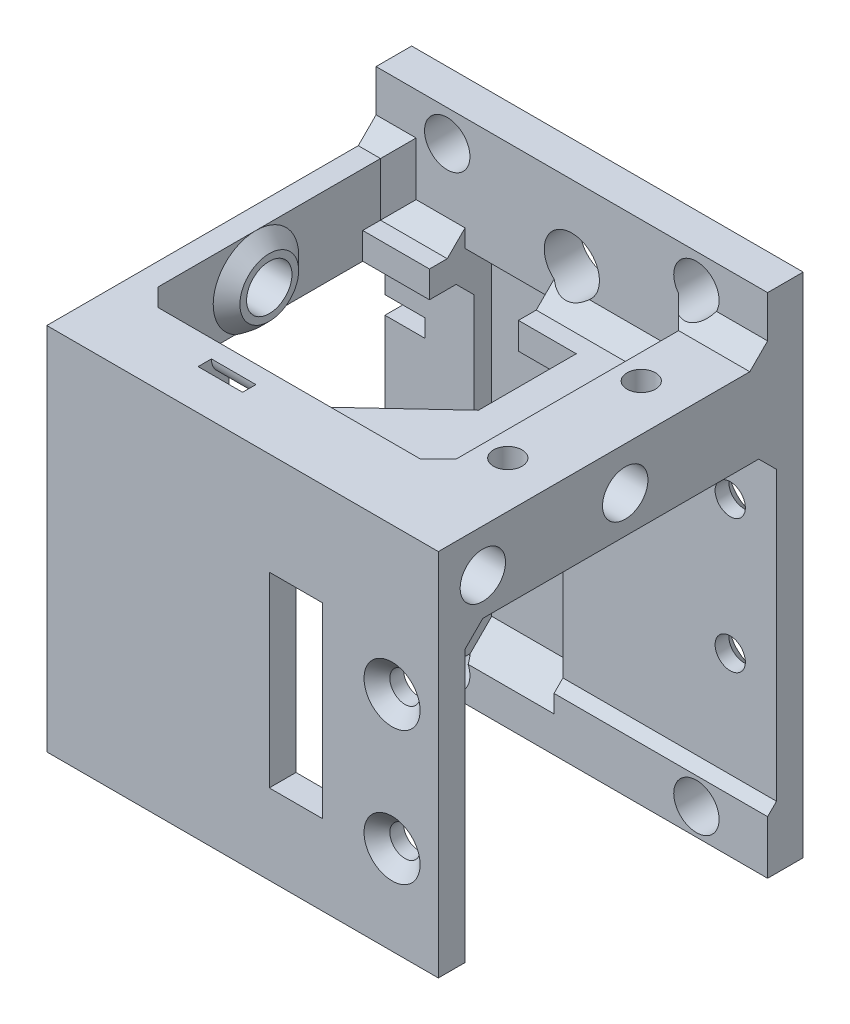
SolidWorks part; units mm, degrees
ref_plane "Front Plane" through (0, 0, 0) normal (0, 0, 1) x (1, 0, 0)
ref_plane "Top Plane" through (0, 0, 0) normal (0, 1, 0) x (1, 0, 0)
ref_plane "Right Plane" through (0, 0, 0) normal (1, 0, 0) x (0, 0, -1)
sketch "Sketch1" plane through (0, 0, 0) normal (0, 1, 0) x (1, 0, 0)
  line L0 (-19.5, 12.5) -> (-19.5, -12.5)
  line L1 (-22, -20.5) -> (22, -20.5)
  line L2 (-22, -20.5) -> (-22, 20.5)
  line L3 (-22, 20.5) -> (22, 20.5)
  line L4 (22, -20.5) -> (22, 20.5)
  line L5 (-22, -20.5) -> (22, 20.5) construction
  line L6 (-22, 20.5) -> (22, -20.5) construction
  line L7 (-19.5, 12.5) -> (4.5, 12.5)
  line L8 (4.5, 12.5) -> (4.5, 1.5)
  line L9 (-19.5, -12.5) -> (-10.5244, -12.5)
  line L10 (-10.5244, -12.5) -> (4.5, 1.5)
  circle A0 centre (16.8, -7.5) radius 1.6
  circle A1 centre (16.8, 7.5) radius 1.6
  point P0 (0, 0)
  dimension "D9" = 3.2
  dimension "D12" = 3.2
  dimension "D1" = 44
  dimension "D2" = 41
  dimension "D3" = 2.5
  dimension "D4" = 25
  dimension "D5" = 8
  dimension "D6" = 24
  dimension "D7" = 11
  dimension "D8" = 5.2
  dimension "D10" = 13
  dimension "D11" = 15
extrude "Boss-Extrude1" add sketch "Sketch1" along normal blind 3
sketch "Sketch2" plane through (0, 3, 0) normal (0, 1, 0) x (1, 0, 0)
  line L0 (-22, 20.5) -> (-22, -20.5) construction
  line L1 (22, 20.5) -> (-22, 20.5)
  line L2 (22, 20.5) -> (22, 16.5)
  line L3 (22, 16.5) -> (-22, 16.5)
  line L4 (-22, 20.5) -> (-22, 16.5)
  dimension "D1" = 4
extrude "Boss-Extrude2" add sketch "Sketch2" along normal blind 12.7
sketch "Sketch3" plane through (0, 0, 0) normal (0, -1, 0) x (1, 0, 0)
  line L0 (22, 20.5) -> (22, -20.5) construction
  line L1 (-22, -20.5) -> (22, -20.5)
  line L2 (-22, -20.5) -> (-22, -17.5)
  line L3 (-22, -17.5) -> (22, -17.5)
  line L4 (22, -20.5) -> (22, -17.5)
  dimension "D1" = 3
extrude "Boss-Extrude3" add sketch "Sketch3" along normal blind 41.3
sketch "Sketch4" plane through (0, 0, 0) normal (0, -1, 0) x (1, 0, 0)
  line L0 (-22, -17.5) -> (-22, 20.5) construction
  line L1 (22, 20.5) -> (-22, 20.5)
  line L2 (22, 20.5) -> (22, 17.5)
  line L3 (22, 17.5) -> (-22, 17.5)
  line L4 (-22, 20.5) -> (-22, 17.5)
  dimension "D1" = 3
extrude "Boss-Extrude4" add sketch "Sketch4" along normal blind 32.5
sketch "Sketch8" plane through (-22, 0, 0) normal (-1, 0, 0) x (0, 0, 1)
  line L0 (-16.5, -35.3) -> (-17.5, -34.3)
  line L1 (-17.5, -41.3) -> (-16.5, -41.3)
  line L2 (-17.5, -41.3) -> (-17.5, -35.3)
  line L3 (-17.5, -35.3) -> (-16.5, -35.3)
  line L4 (-16.5, -41.3) -> (-16.5, -35.3)
  line L5 (-17.5, -41.3) -> (-17.5, 0) construction
  line L6 (-17.5, -34.3) -> (-17.5, -35.3)
  line M5 (-17.5, -41.3) -> (-17.5, 0)
  dimension "D1" = 1
  dimension "D2" = 6
extrude "Boss-Extrude6" add sketch "Sketch8" against normal up to surface (44 mm away) contours L1 L4 L3 M5 | L3 L0 M5 region at (-22, -34.9667, -17.1667) region at (-22, -38.3, -17) up to face at (22, -11.02, -3.3)
sketch "Sketch9" plane through (0, 0, 20.5) normal (0, 0, 1) x (1, 0, 0)
  line L0 (-22, 3) -> (-22, -32.5) construction
  line L1 (3, -23.5) -> (9, -23.5)
  line L2 (3, -23.5) -> (3, -2.5)
  line L3 (3, -2.5) -> (9, -2.5)
  line L4 (9, -23.5) -> (9, -2.5)
  line L5 (22, -32.5) -> (-22, -32.5) construction
  line L6 (22, 3) -> (22, -32.5) construction
  circle A0 centre (16.8, -7.5) radius 1.6
  circle A1 centre (16.8, -22.5) radius 1.6
  dimension "D5" = 3.2
  dimension "D6" = 3.2
  dimension "D1" = 25
  dimension "D2" = 6
  dimension "D3" = 21
  dimension "D4" = 9
  dimension "D7" = 5.2
  dimension "D8" = 5.2
  dimension "D9" = 15
  dimension "D10" = 10
extrude "Cut-Extrude2" cut sketch "Sketch9" against normal up to next
sketch "Sketch12" plane through (0, 3, 0) normal (0, 1, 0) x (1, 0, 0)
  line L0 (-22, 16.5) -> (-22, -20.5) construction
  line L1 (22, -20.5) -> (-22, -20.5)
  line L2 (22, -20.5) -> (22, -12.5)
  line L3 (22, -12.5) -> (-22, -12.5)
  line L4 (-22, -20.5) -> (-22, -12.5)
  line L5 (-19.5, -12.5) -> (-10.5244, -12.5) construction
  line L6 (-19.5, 12.5) -> (-19.5, -12.5) construction
  line L7 (-22, 16.5) -> (-19.5, 16.5)
  line L8 (-22, 16.5) -> (-22, -12.5)
  line L9 (-22, -12.5) -> (-19.5, -12.5)
  line L10 (-19.5, 16.5) -> (-19.5, -12.5)
  line L11 (-22, 16.5) -> (22, 16.5) construction
  line L12 (22, -12.5) -> (14, -12.5)
  line L13 (22, -12.5) -> (22, 16.5)
  line L14 (22, 16.5) -> (14, 16.5)
  line L15 (14, -12.5) -> (14, 16.5)
  circle M6 centre (16.8, 7.5) radius 1.6
  circle M7 centre (16.8, -7.5) radius 1.6
  line M11 (-10.5244, -12.5) -> (-19.5, -12.5)
  line M12 (-19.5, -12.5) -> (-19.5, 12.5)
  line M13 (22, 16.5) -> (-22, 16.5)
  line M14 (-22, 16.5) -> (-22, -20.5)
  line M15 (-22, -20.5) -> (22, -20.5)
  line M16 (22, -20.5) -> (22, 16.5)
  dimension "D1" = 8
extrude "Boss-Extrude7" add sketch "Sketch12" along normal blind 6 contours L15 L3 M16 M13 M7 M6 | L3 M16 M11 M14 M15 | L10 L3 M13 M14 M12 region at (0, 3, 16.5) region at (18.0894, 3, -2.149) region at (-20.75, 3, -2)
sketch "Sketch13" plane through (-22, 0, 0) normal (-1, 0, 0) x (0, 0, 1)
  line L0 (20.5, 9) -> (20.5, -32.5) construction
  line L1 (-17.5, 0) -> (17.5, 0) construction
  line L2 (-17.5, -34.3) -> (-17.5, 0) construction
  circle A0 centre (15.5, 4.2) radius 2.55
  circle A1 centre (-0.5, 4.2) radius 2.55
  dimension "D3" = 5.1
  dimension "D5" = 5.1
  dimension "D1" = 5
  dimension "D2" = 4.2
  dimension "D4" = 17
extrude "Cut-Extrude3" cut sketch "Sketch13" against normal blind 6
sketch "Sketch14" plane through (-19.5, 0, 0) normal (1, 0, 0) x (0, 0, -1)
  circle A0 centre (0.5, 4.2) radius 3.3
  circle A1 centre (0.5, 4.2) radius 2.55
  dimension "D1" = 6.6
extrude "Boss-Extrude9" add sketch "Sketch14" along normal blind 1.5
mirror "Mirror1" about plane through (0, 0, 0) normal (1, 0, 0) of "Cut-Extrude3"
sketch "Sketch15" plane through (0, 0, 20.5) normal (0, 0, 1) x (1, 0, 0)
  point P0 (16.8, -7.5)
  point P1 (16.8, -22.5)
hole_wizard "CSK for M3 Flat Head Machine Screw1" positions "Sketch18" profile "Sketch19" countersink size "M3" standard "ANSI Metric" end condition through all
sketch "Sketch18" plane through (0, 0, 20.5) normal (0, 0, 1) x (1, 0, 0)
  point P0 (16.8, -7.5)
  point P3 (16.8, -22.5)
sketch "Sketch19" plane through (16.8, -7.5, 20.5) normal (1, 0, 0) x (0, -1, 0)
  line L0 (0, 0) -> (0, 41)
  line L1 (0, 41) -> (1.7, 41)
  line L2 (1.7, 41) -> (1.7, 1.45)
  line L3 (1.7, 1.45) -> (3.15, 0)
  line L5 (3.15, 0) -> (0, 0)
  line L6 (-1.7, 1.45) -> (-3.15, 0) construction
  line L11 (0, -6.35) -> (0, 107.95) construction
  dimension "Thru Hole Dia." = 3.4
  dimension "Thru Hole Depth" = 41
  dimension "Near C'Sink Dia." = 6.3
  dimension "Near C'Sink Angle" = 90
sketch "Sketch20" plane through (0, 0, -20.5) normal (0, 0, -1) x (-1, 0, 0)
  point P0 (-16.8, -7.5)
  point P1 (-16.8, -22.5)
hole_wizard "CSK for M3 Flat Head Machine Screw2" positions "Sketch21" profile "Sketch22" countersink size "M3" standard "ANSI Metric" end condition through all
sketch "Sketch21" plane through (0, 0, -20.5) normal (0, 0, -1) x (-1, 0, 0)
  point P0 (-16.8, -7.5)
  point P3 (-16.8, -22.5)
sketch "Sketch22" plane through (16.8, -7.5, -20.5) normal (1, 0, 0) x (0, 1, 0)
  line L0 (0, 0) -> (0, 41)
  line L1 (0, 41) -> (1.7, 41)
  line L2 (1.7, 41) -> (1.7, 1.45)
  line L3 (1.7, 1.45) -> (3.15, 0)
  line L5 (3.15, 0) -> (0, 0)
  line L6 (-1.7, 1.45) -> (-3.15, 0) construction
  line L11 (0, -6.35) -> (0, 107.95) construction
  dimension "Thru Hole Dia." = 3.4
  dimension "Thru Hole Depth" = 41
  dimension "Near C'Sink Dia." = 6.3
  dimension "Near C'Sink Angle" = 90
sketch "Sketch23" plane through (0, 0, -17.5) normal (0, 0, 1) x (1, 0, 0)
  line L0 (22, -34.3) -> (-22, -34.3) construction
  line L1 (-2, 3) -> (-12, 3)
  line L2 (-2, 3) -> (-2, -34.3)
  line L3 (-2, -34.3) -> (-12, -34.3)
  line L4 (-12, 3) -> (-12, -34.3)
  line L5 (-2, 3) -> (-12, -34.3) construction
  line L6 (-2, -34.3) -> (-12, 3) construction
  line L9 (-22, -34.3) -> (-22, 0) construction
  line L11 (14, 3) -> (-10.5244, 3) construction
  point P0 (-7, -15.65)
  dimension "D1" = 10
  dimension "D2" = 15
extrude "Cut-Extrude4" cut sketch "Sketch23" against normal blind 2 and the other way up to next
chamfer "Chamfer2" distance 1.5 1 edges at (-19.5, 4.2, -3.8)
chamfer "Chamfer3" distance 2 12 edges at (6, 3, -16.5) (10, 0, -17.5) (-17, 0, -17.5) (0, 0, 17.5) (18, 9, -16.5) (-20.75, 9, -16.5) (-7, 3, -19.5) (-15.75, 3, -16.5) (-19.5, 4.5, 12.5) (14, 6, 12.5) (14, 6, -16.5) (-19.5, 6, -16.5)
sketch "Sketch5" plane through (0, 0, -20.5) normal (0, 0, -1) x (-1, 0, 0)
  line L0 (0, -41.3) -> (0, 15.7) construction
  line L1 (22, -41.3) -> (-22, -41.3) construction
  line L2 (-22, 15.7) -> (22, 15.7) construction
  circle A0 centre (-14, -38.3) radius 2.55
  circle A1 centre (14, -38.3) radius 2.55
  circle A2 centre (-14, 12.2) radius 2.55
  circle A3 centre (14, 12.2) radius 2.55
  circle A4 centre (0, 7.4) radius 3.1
  dimension "D1" = 5.1
  dimension "D4" = 5.1
  dimension "D7" = 6.2
  dimension "D2" = 3
  dimension "D3" = 14
  dimension "D5" = 50.5
  dimension "D6" = 8.3
extrude "Cut-Extrude1" cut sketch "Sketch5" against normal up to next
sketch "Sketch24" plane through (-2, 0, 0) normal (-1, 0, 0) x (0, 0, 1)
  line L3 (-17.5, -34.3) -> (-19.5, -34.3)
  line L5 (-16.5, -40.85) -> (-16.5, -35.75) construction
  line L6 (-16.5, -37.3) -> (-16.5, -35.3)
  line L7 (-16.5, -41.3) -> (-16.5, -35.3) construction
  line L8 (-19.5, -34.3) -> (-16.5, -37.3)
  line L9 (-16.5, -35.3) -> (-17.5, -34.3)
extrude "Cut-Extrude9" cut sketch "Sketch24" along normal up to surface (10 mm away) up to face at (-12, -4.7818, -16.3182)
sketch "Sketch25" plane through (0, 0, 12.5) normal (0, 0, -1) x (-1, 0, 0)
  line L0 (22, 15.7) -> (22, -41.3) construction
  line L1 (9.5, 7) -> (4.5, 7)
  line L2 (9.5, 7) -> (9.5, 5.5)
  line L3 (9.5, 5.5) -> (4.5, 5.5)
  line L4 (4.5, 7) -> (4.5, 5.5)
  line L5 (9.5, 7) -> (4.5, 5.5) construction
  line L6 (9.5, 5.5) -> (4.5, 7) construction
  line L7 (-12, 9) -> (17.5, 9) construction
  point P0 (7, 6.25)
  dimension "D1" = 15
  dimension "D2" = 5
  dimension "D3" = 1.5
  dimension "D4" = 2
sketch "Sketch26" plane through (0, 0, -20.5) normal (0, 0, -1) x (-1, 0, 0)
  line L0 (22, 15.7) -> (22, -41.3) construction
  line L1 (22, -7) -> (17.5, -7)
  line L2 (22, -7) -> (22, -9)
  line L3 (22, -9) -> (17.5, -9)
  line L4 (17.5, -7) -> (17.5, -9)
  line L6 (22.55, 0) -> (-22.55, 0) construction
  dimension "D1" = 7
  dimension "D2" = 2
  dimension "D3" = 4.5
extrude "Cut-Extrude11" cut sketch "Sketch26" against normal up to next
revolve "Cut-Revolve1" cut sketch "Sketch25" angle 90 about axis through (0, 9, 12.5) along (-1, 0, 0)
